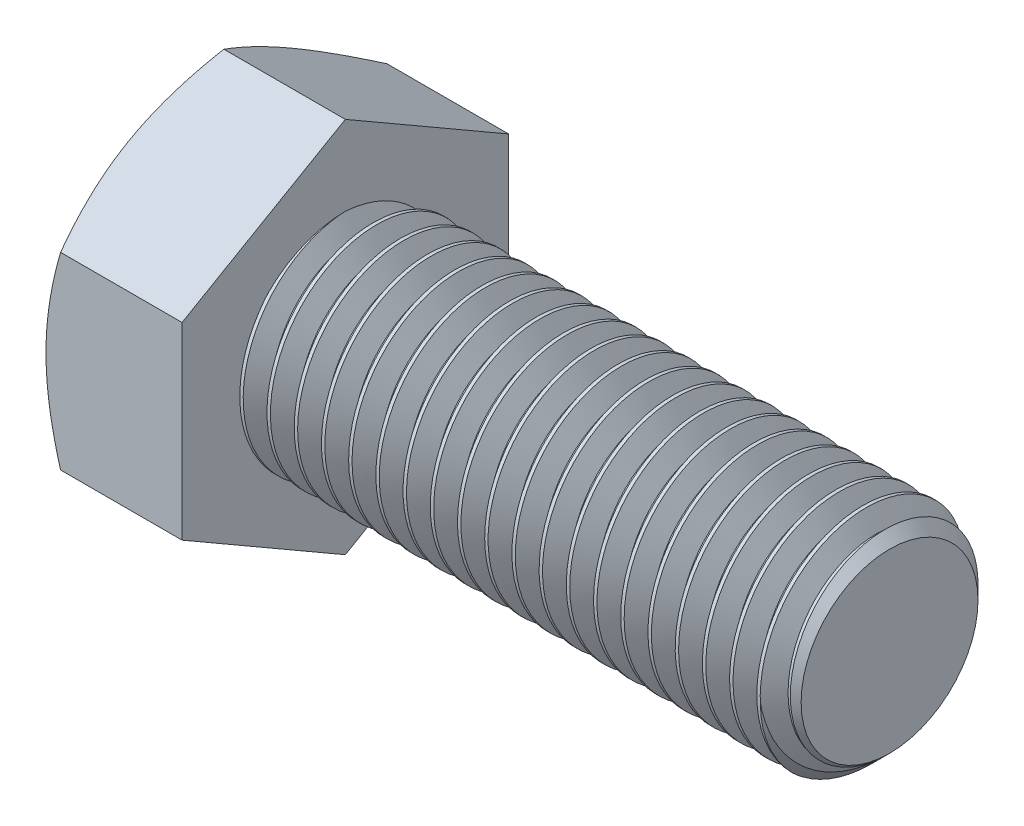
SolidWorks part; units mm, degrees
ref_plane "Front Plane" through (0, 0, 0) normal (0, 0, 1) x (1, 0, 0)
ref_plane "Top Plane" through (0, 0, 0) normal (0, 1, 0) x (1, 0, 0)
ref_plane "Right Plane" through (0, 0, 0) normal (1, 0, 0) x (0, 0, -1)
sketch "Sketch1" plane through (0, 0, 0) normal (0, 0, 1) x (1, 0, 0)
  line L0 (-31.25, 0) -> (31.25, 0) construction
  line L1 (-18.75, 15) -> (-18.75, -15) construction
  line L2 (-31.25, 15) -> (-31.25, -15) construction
  line L3 (31.25, 10) -> (31.25, -10) construction
  point P8 (22.5, -10)
  dimension "Thread Dia" = 20
  dimension "Hex" = 30
  dimension "Head Ht" = 12.5
  dimension "Length" = 50
  dimension "D1" = 8.75
ref_plane "Plane2" through (31.25, 0, 0) normal (1, 0, 0) x (0, 0, -1)
sketch "Sketch2" plane through (31.25, 0, 0) normal (1, 0, 0) x (0, 0, -1)
  circle A0 centre (0, 0) radius 10
extrude "Boss-Extrude1" add sketch "Sketch2" against normal up to vertex (50 mm away) up to point (-18.75, -15, 0)
sketch "Sketch4" plane through (31.25, 0, 0) normal (1, 0, 0) x (0, 0, -1)
  circle A1 centre (0, 0) radius 10
  circle A2 centre (0, 0) radius 10
  dimension "D1" = 0
curve "Helix/Spiral1" pitch 2.5 height 52.5 turns 21 parameters "Pitch"=2.5
chamfer "Chamfer1" distance 1.875 angle 45 1 edges at (31.25, 0, -10)
sketch "Sketch5" plane through (0, 0, 0) normal (0, 0, 1) x (1, 0, 0)
  line L0 (31.25, 10) -> (32.1875, 8.3762)
  line L1 (32.1875, 8.3762) -> (32.5, 8.3762)
  line L2 (32.5, 8.3762) -> (33.4375, 10)
  line L3 (31.25, 10) -> (33.4375, 10)
  line L4 (32.3438, 8.3762) -> (32.3438, 10) construction
  line L5 (31.7188, 9.1881) -> (32.9688, 9.1881) construction
  line L6 (31.25, -10) -> (31.25, 10) construction
  dimension "D1" = 60
  dimension "D2" = 0.3125
  dimension "D3" = 1.25
sweep "Cut-Sweep1" cut profiles "Sketch5" path "Helix/Spiral1" align with end faces yes
sketch "Sketch3" plane through (-18.75, 0, 0) normal (-1, 0, 0) x (0, 0, 1)
  line L0 (0, 15) -> (0, -15) construction
  line L1 (-15, -8.6603) -> (0, -17.3205)
  line L2 (0, -17.3205) -> (15, -8.6603)
  line L3 (15, -8.6603) -> (15, 8.6603)
  line L4 (15, 8.6603) -> (0, 17.3205)
  line L5 (0, 17.3205) -> (-15, 8.6603)
  line L6 (-15, 8.6603) -> (-15, -8.6603)
  circle A0 centre (0, 0) radius 15 construction
extrude "Boss-Extrude2" add sketch "Sketch3" along normal up to vertex (12.5 mm away) up to point (-31.25, -15, 0)
sketch "Sketch6" plane through (-31.25, 0, 0) normal (-1, 0, 0) x (0, 0, 1)
  circle A0 centre (0, 0) radius 15 construction
  circle A1 centre (0, 0) radius 15
extrude "Cut-Extrude1" cut sketch "Sketch6" against normal through all draft 60 flip side to cut
sketch "Sketch9" plane through (0, 0, 0) normal (0, 0, 1) x (1, 0, 0)
  line L0 (-18.75, 10) -> (-18.75, 0)
  line L1 (-18.75, 0) -> (-12.75, 0)
  line L2 (-12.75, 0) -> (-22.75, 10)
  line L3 (-22.75, 10) -> (-18.75, 10)
  line L4 (-31.25, 0) -> (31.25, 0) construction
  line L5 (-18.75, 15) -> (-18.75, -15) construction
  line L6 (31.25, 10) -> (31.25, -10) construction
  dimension "D1" = 45
  dimension "MinThreadLg" = 54
revolve "Revolve1" [suppressed] add sketch "Sketch9" angle 360 about L1
equation "\"D2@Sketch5\" = \"Pitch@Helix/Spiral1\"*.125"
equation "\"D3@Sketch5\" = \"Pitch@Helix/Spiral1\"*.50"
equation "\"D3@Helix/Spiral1\" = \"Length@Sketch1\"+\"Pitch@Helix/Spiral1\""
equation "\"D1@Chamfer1\" = \"Pitch@Helix/Spiral1\"*.750"
equation "\"D1@Sketch1\" = \"Pitch@Helix/Spiral1\"*3.50"
